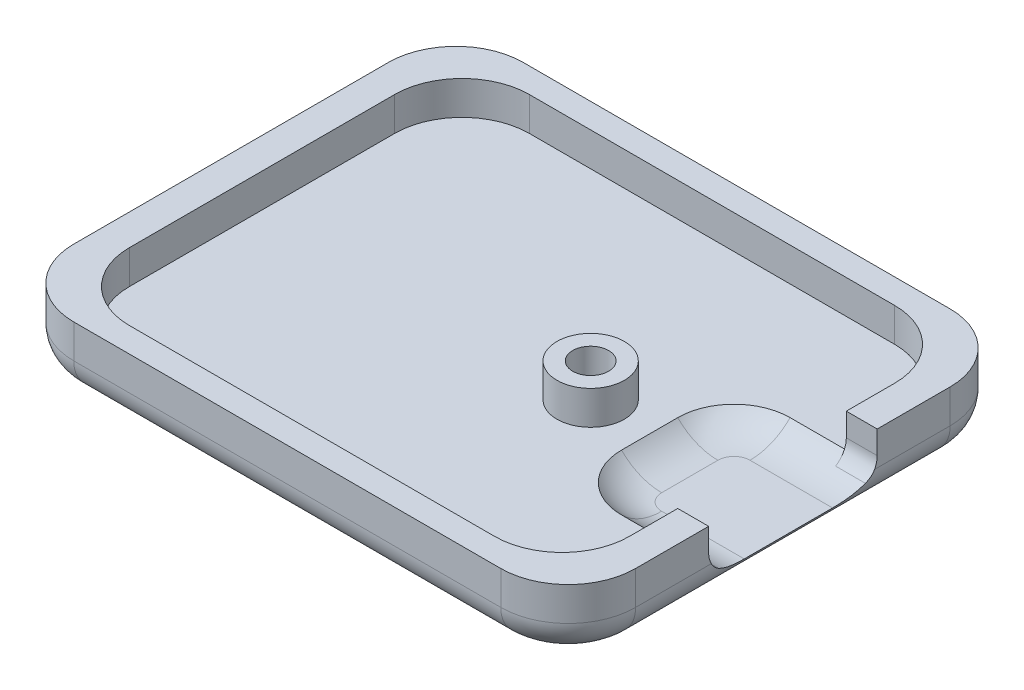
SolidWorks part; units mm, degrees
ref_plane "Front Plane" through (0, 0, 0) normal (0, 0, 1) x (1, 0, 0)
ref_plane "Top Plane" through (0, 0, 0) normal (0, 1, 0) x (1, 0, 0)
ref_plane "Right Plane" through (0, 0, 0) normal (1, 0, 0) x (0, 0, -1)
sketch "Sketch1" plane through (0, 0, 0) normal (0, 1, 0) x (1, 0, 0)
  line L1 (25, -20) -> (-25, -20)
  line L2 (25, -20) -> (25, 20)
  line L3 (25, 20) -> (-25, 20)
  line L4 (-25, -20) -> (-25, 20)
  line L5 (25, -20) -> (-25, 20) construction
  line L6 (25, 20) -> (-25, -20) construction
  line L7 (-22.25, -17.8) -> (22.25, -17.8)
  line L8 (-22.25, -17.8) -> (-22.25, 17.8)
  line L9 (-22.25, 17.8) -> (22.25, 17.8)
  line L10 (22.25, -17.8) -> (22.25, 17.8)
  line L11 (-22.25, -17.8) -> (22.25, 17.8) construction
  line L12 (-22.25, 17.8) -> (22.25, -17.8) construction
  point P0 (0, 0)
  point P6 (0, 0)
  dimension "D1" = 50
  dimension "D2" = 40
  dimension "D3" = 44.5
extrude "Boss-Extrude1" add sketch "Sketch1" along normal blind 6
sketch "Sketch2" plane through (0, 0, 0) normal (0, -1, 0) x (-1, 0, 0)
  line L1 (22.25, 17.8) -> (-22.25, 17.8)
  line L2 (22.25, 17.8) -> (22.25, -17.8)
  line L3 (22.25, -17.8) -> (-22.25, -17.8)
  line L4 (-22.25, 17.8) -> (-22.25, -17.8)
  line L5 (22.25, 17.8) -> (-22.25, -17.8) construction
  line L6 (22.25, -17.8) -> (-22.25, 17.8) construction
  point P0 (0, 0)
extrude "Boss-Extrude2" add sketch "Sketch2" against normal blind 3
sketch "Sketch3" plane through (0, 3, 0) normal (0, 1, 0) x (1, 0, 0)
  line L0 (22.25, 17.8) -> (22.25, -17.8) construction
  circle A0 centre (7, 0) radius 3
  dimension "D1" = 6
  dimension "D2" = 15.25
extrude "Boss-Extrude3" add sketch "Sketch3" along normal up to surface (3 mm away) up to face at (0, 6, 0)
sketch "Sketch4" plane through (0, 6, 0) normal (0, 1, 0) x (1, 0, 0)
  circle A0 centre (7, 0) radius 1.6
  dimension "D1" = 3.2
extrude "Cut-Extrude1" cut sketch "Sketch4" against normal up to surface (6 mm away) up to face at (0, 0, 0)
fillet "Fillet1" radius 6 8 edges at (-25, 3, -20) (-25, 3, 20) (25, 3, 20) (25, 3, -20) (-22.25, 4.5, -17.8) (-22.25, 4.5, 17.8) (22.25, 4.5, 17.8) (22.25, 4.5, -17.8)
chamfer "Chamfer1" distance 1.5 angle 45 1 edges at (7, 0, 1.6)
fillet "Fillet2" radius 3 8 edges at (-23.2426, 0, -18.2426) (0, 0, -20) (23.2426, 0, -18.2426) (25, 0, 0) (23.2426, 0, 18.2426) (0, 0, 20) (-23.2426, 0, 18.2426) (-25, 0, 0)
sketch "Sketch5" plane through (0, 3, 0) normal (0, 1, 0) x (1, 0, 0)
  line L0 (22.25, 11.8) -> (22.25, -11.8) construction
  line L5 (12.25, 7.5) -> (22.25, -7.5) construction
  line L6 (12.25, -7.5) -> (22.25, 7.5) construction
  line L7 (25, -14) -> (25, 14) construction
  line L8 (12.25, 7.5) -> (25, 7.5)
  line L9 (12.25, 7.5) -> (12.25, -7.5)
  line L10 (12.25, -7.5) -> (25, -7.5)
  line L11 (25, 7.5) -> (25, -7.5)
  circle A0 centre (7, 0) radius 1.6 construction
  point P0 (17.25, 0)
  dimension "D1" = 10
  dimension "D2" = 15
  dimension "D3" = 0
extrude "Cut-Extrude2" cut sketch "Sketch5" against normal blind 1.5 and the other way up to surface (3 mm away) other way up to face at (0, 6, 0)
fillet "Fillet3" radius 5 2 edges at (12.25, 2.25, 7.5) (12.25, 2.25, -7.5)
fillet "Fillet4" radius 5 5 edges at (20.924, 1.5, 7.5) (13.7145, 1.5, 6.0355) (12.25, 1.5, 0) (13.7145, 1.5, -6.0355) (20.924, 1.5, -7.5)
fillet "Fillet5" radius 2 2 edges at (23.625, 3, 7.5) (23.625, 3, -7.5)
